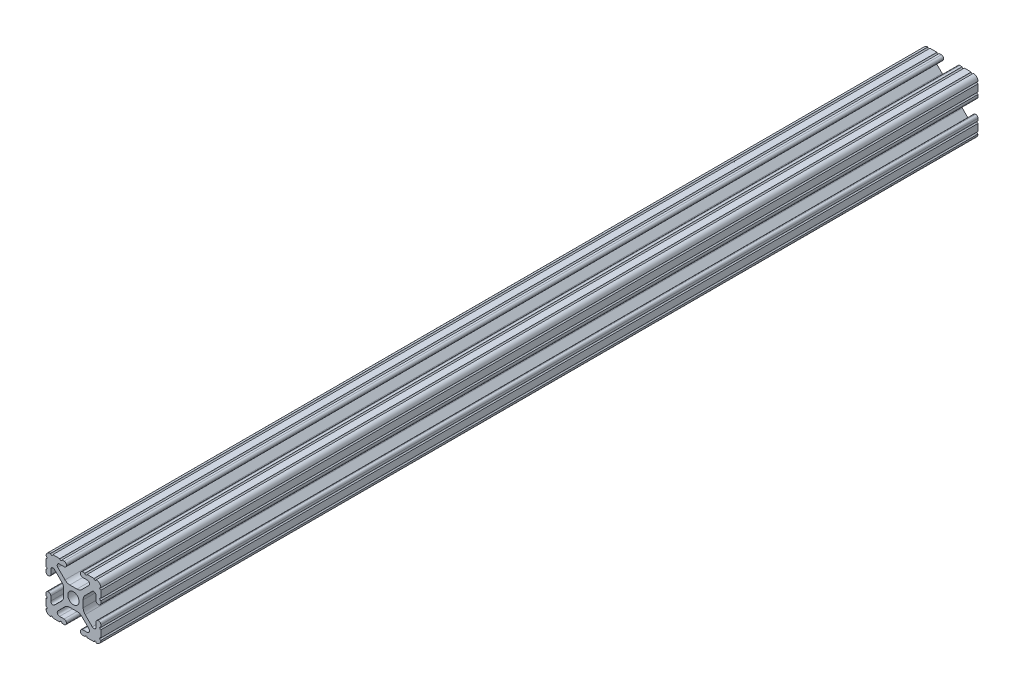
SolidWorks part; units mm, degrees
ref_plane "Front Plane" through (0, 0, 0) normal (0, 0, 1) x (1, 0, 0)
ref_plane "Top Plane" through (0, 0, 0) normal (0, 1, 0) x (1, 0, 0)
ref_plane "Right Plane" through (0, 0, 0) normal (1, 0, 0) x (0, 0, -1)
sketch "Sketch1" plane through (0, 0, 0) normal (0, 0, 1) x (1, 0, 0)
  line L88 (-7.1797, -8.6452) -> (-3.9523, -5.4237)
  line L89 (-1.7093, -4.4958) -> (1.7093, -4.4958)
  line L90 (3.9523, -5.4237) -> (7.1797, -8.6452)
  line L91 (6.4164, -10.4902) -> (4.2875, -10.4902)
  line L92 (3.2385, -11.5392) -> (3.2385, -11.651)
  line L93 (4.2875, -12.7) -> (5.3171, -12.7)
  line L94 (6.3331, -12.7) -> (9.5504, -12.7)
  line L95 (12.7, -9.5504) -> (12.7, -6.3331)
  line L96 (12.7, -5.3171) -> (12.7, -4.2875)
  line L97 (11.651, -3.2385) -> (11.5392, -3.2385)
  line L98 (10.4902, -4.2875) -> (10.4902, -6.4021)
  line L99 (8.7371, -7.1294) -> (5.441, -3.8408)
  line L100 (4.5085, -1.5932) -> (4.5085, 1.5932)
  line L101 (5.441, 3.8408) -> (8.7371, 7.1294)
  line L102 (10.4902, 6.4021) -> (10.4902, 4.2875)
  line L103 (11.5392, 3.2385) -> (11.651, 3.2385)
  line L104 (12.7, 4.2875) -> (12.7, 5.3171)
  line L105 (12.7, 6.3331) -> (12.7, 9.5504)
  line L106 (9.5504, 12.7) -> (6.3331, 12.7)
  line L107 (5.3171, 12.7) -> (4.2875, 12.7)
  line L108 (3.2385, 11.651) -> (3.2385, 11.5392)
  line L109 (4.2875, 10.4902) -> (6.4768, 10.4902)
  line L110 (7.207, 8.7244) -> (3.8983, 5.4232)
  line L111 (1.6558, 4.4958) -> (-1.6558, 4.4958)
  line L112 (-3.8983, 5.4232) -> (-7.207, 8.7244)
  line L113 (-6.4768, 10.4902) -> (-4.2875, 10.4902)
  line L114 (-3.2385, 11.5392) -> (-3.2385, 11.651)
  line L115 (-4.2875, 12.7) -> (-5.3171, 12.7)
  line L116 (-6.3331, 12.7) -> (-9.5504, 12.7)
  line L117 (-12.7, 9.5504) -> (-12.7, 6.3331)
  line L118 (-12.7, 5.3171) -> (-12.7, 4.2875)
  line L119 (-11.651, 3.2385) -> (-11.5392, 3.2385)
  line L120 (-10.4902, 4.2875) -> (-10.4902, 6.4021)
  line L121 (-8.7371, 7.1294) -> (-5.441, 3.8408)
  line L122 (-4.5085, 1.5932) -> (-4.5085, -1.5932)
  line L123 (-5.441, -3.8408) -> (-8.7371, -7.1294)
  line L124 (-10.4902, -6.4021) -> (-10.4902, -4.2875)
  line L125 (-11.5392, -3.2385) -> (-11.651, -3.2385)
  line L126 (-12.7, -4.2875) -> (-12.7, -5.3171)
  line L127 (-12.7, -6.3331) -> (-12.7, -9.5504)
  line L128 (-9.5504, -12.7) -> (-6.3331, -12.7)
  line L129 (-5.3171, -12.7) -> (-4.2875, -12.7)
  line L130 (-3.2385, -11.651) -> (-3.2385, -11.5392)
  line L131 (-4.2875, -10.4902) -> (-6.4164, -10.4902)
  circle A1 centre (0, 0) radius 2.6035
  arc A104 (-7.1797, -8.6452) -> (-6.4164, -10.4902) centre (-6.4164, -9.4098) ccw
  arc A105 (-1.7093, -4.4958) -> (-3.9523, -5.4237) centre (-1.7093, -7.6708) ccw
  arc A106 (3.9523, -5.4237) -> (1.7093, -4.4958) centre (1.7093, -7.6708) ccw
  arc A107 (6.4164, -10.4902) -> (7.1797, -8.6452) centre (6.4164, -9.4098) ccw
  arc A108 (4.2875, -10.4902) -> (3.2385, -11.5392) centre (4.2875, -11.5392) ccw
  arc A109 (3.2385, -11.651) -> (4.2875, -12.7) centre (4.2875, -11.651) ccw
  arc A110 (6.3331, -12.7) -> (5.3171, -12.7) centre (5.8251, -12.7) ccw
  arc A111 (10.5664, -12.6998) -> (9.5504, -12.7) centre (10.0584, -12.7) ccw
  arc A112 (10.5664, -12.6998) -> (12.6998, -10.5664) centre (10.5918, -10.5918) ccw
  arc A113 (12.7, -9.5504) -> (12.6998, -10.5664) centre (12.7, -10.0584) ccw
  arc A114 (12.7, -5.3171) -> (12.7, -6.3331) centre (12.7, -5.8251) ccw
  arc A115 (12.7, -4.2875) -> (11.651, -3.2385) centre (11.651, -4.2875) ccw
  arc A116 (11.5392, -3.2385) -> (10.4902, -4.2875) centre (11.5392, -4.2875) ccw
  arc A117 (8.7371, -7.1294) -> (10.4902, -6.4021) centre (9.4628, -6.4021) ccw
  arc A118 (4.5085, -1.5932) -> (5.441, -3.8408) centre (7.6835, -1.5932) ccw
  arc A119 (5.441, 3.8408) -> (4.5085, 1.5932) centre (7.6835, 1.5932) ccw
  arc A120 (10.4902, 6.4021) -> (8.7371, 7.1294) centre (9.4628, 6.4021) ccw
  arc A121 (10.4902, 4.2875) -> (11.5392, 3.2385) centre (11.5392, 4.2875) ccw
  arc A122 (11.651, 3.2385) -> (12.7, 4.2875) centre (11.651, 4.2875) ccw
  arc A123 (12.7, 6.3331) -> (12.7, 5.3171) centre (12.7, 5.8251) ccw
  arc A124 (12.6998, 10.5664) -> (12.7, 9.5504) centre (12.7, 10.0584) ccw
  arc A125 (12.6998, 10.5664) -> (10.5664, 12.6998) centre (10.5918, 10.5918) ccw
  arc A126 (9.5504, 12.7) -> (10.5664, 12.6998) centre (10.0584, 12.7) ccw
  arc A127 (5.3171, 12.7) -> (6.3331, 12.7) centre (5.8251, 12.7) ccw
  arc A128 (4.2875, 12.7) -> (3.2385, 11.651) centre (4.2875, 11.651) ccw
  arc A129 (3.2385, 11.5392) -> (4.2875, 10.4902) centre (4.2875, 11.5392) ccw
  arc A130 (7.207, 8.7244) -> (6.4768, 10.4902) centre (6.4768, 9.4563) ccw
  arc A131 (1.6558, 4.4958) -> (3.8983, 5.4232) centre (1.6558, 7.6708) ccw
  arc A132 (-3.8983, 5.4232) -> (-1.6558, 4.4958) centre (-1.6558, 7.6708) ccw
  arc A133 (-6.4768, 10.4902) -> (-7.207, 8.7244) centre (-6.4768, 9.4563) ccw
  arc A134 (-4.2875, 10.4902) -> (-3.2385, 11.5392) centre (-4.2875, 11.5392) ccw
  arc A135 (-3.2385, 11.651) -> (-4.2875, 12.7) centre (-4.2875, 11.651) ccw
  arc A136 (-6.3331, 12.7) -> (-5.3171, 12.7) centre (-5.8251, 12.7) ccw
  arc A137 (-10.5664, 12.6998) -> (-9.5504, 12.7) centre (-10.0584, 12.7) ccw
  arc A138 (-10.5664, 12.6998) -> (-12.6998, 10.5664) centre (-10.5918, 10.5918) ccw
  arc A139 (-12.7, 9.5504) -> (-12.6998, 10.5664) centre (-12.7, 10.0584) ccw
  arc A140 (-12.7, 5.3171) -> (-12.7, 6.3331) centre (-12.7, 5.8251) ccw
  arc A141 (-12.7, 4.2875) -> (-11.651, 3.2385) centre (-11.651, 4.2875) ccw
  arc A142 (-11.5392, 3.2385) -> (-10.4902, 4.2875) centre (-11.5392, 4.2875) ccw
  arc A143 (-8.7371, 7.1294) -> (-10.4902, 6.4021) centre (-9.4628, 6.4021) ccw
  arc A144 (-4.5085, 1.5932) -> (-5.441, 3.8408) centre (-7.6835, 1.5932) ccw
  arc A145 (-5.441, -3.8408) -> (-4.5085, -1.5932) centre (-7.6835, -1.5932) ccw
  arc A146 (-10.4902, -6.4021) -> (-8.7371, -7.1294) centre (-9.4628, -6.4021) ccw
  arc A147 (-10.4902, -4.2875) -> (-11.5392, -3.2385) centre (-11.5392, -4.2875) ccw
  arc A148 (-11.651, -3.2385) -> (-12.7, -4.2875) centre (-11.651, -4.2875) ccw
  arc A149 (-12.7, -6.3331) -> (-12.7, -5.3171) centre (-12.7, -5.8251) ccw
  arc A150 (-12.6998, -10.5664) -> (-12.7, -9.5504) centre (-12.7, -10.0584) ccw
  arc A151 (-12.6998, -10.5664) -> (-10.5664, -12.6998) centre (-10.5918, -10.5918) ccw
  arc A152 (-9.5504, -12.7) -> (-10.5664, -12.6998) centre (-10.0584, -12.7) ccw
  arc A153 (-5.3171, -12.7) -> (-6.3331, -12.7) centre (-5.8251, -12.7) ccw
  arc A154 (-4.2875, -12.7) -> (-3.2385, -11.651) centre (-4.2875, -11.651) ccw
  arc A155 (-3.2385, -11.5392) -> (-4.2875, -10.4902) centre (-4.2875, -11.5392) ccw
extrude "Boss-Extrude1" add sketch "Sketch1" along normal mid plane 609.6
sketch "Sketch2" plane through (0, 0, 304.8) normal (0, 0, 1) x (1, 0, 0)
  circle A0 centre (0, 0) radius 37.7136
extrude "Cut-Extrude1" cut sketch "Sketch2" against normal blind 203.2
ref_axis "Axis1" through (0, 0, 101.6) along (0, 0, -1)
